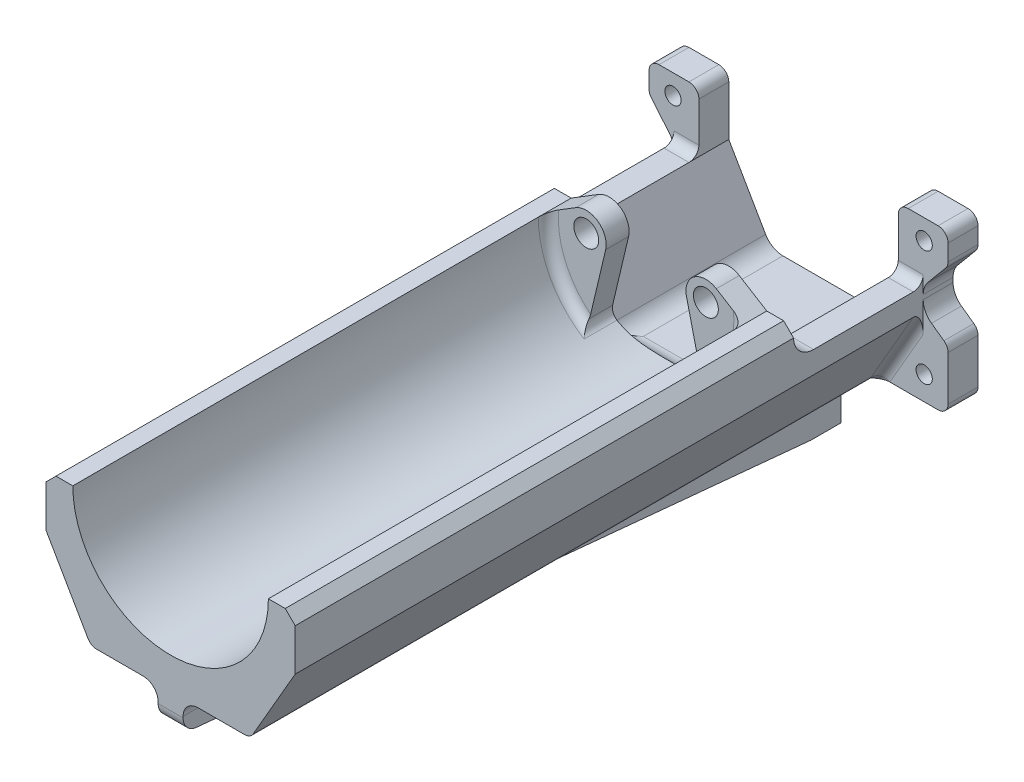
SolidWorks part; units mm, degrees
ref_plane "Front Plane" through (0, 0, 0) normal (0, 0, 1) x (1, 0, 0)
ref_plane "Top Plane" through (0, 0, 0) normal (0, 1, 0) x (1, 0, 0)
ref_plane "Right Plane" through (0, 0, 0) normal (1, 0, 0) x (0, 0, -1)
sketch "Sketch1" plane through (0, 0, 0) normal (0, 0, 1) x (1, 0, 0)
  line L0 (-12.4587, 0) -> (-15.875, 0)
  line L1 (-15.875, 0) -> (-15.875, -16.51)
  line L2 (-15.875, -16.51) -> (15.875, -16.51)
  line L3 (15.875, -16.51) -> (15.875, 0)
  line L4 (15.875, 0) -> (12.4587, 0)
  arc A0 (-12.4587, 0) -> (12.4587, 0) centre (0, 0) ccw
  dimension "D1" = 24.9174
  dimension "D2" = 31.75
  dimension "D3" = 16.51
extrude "Boss-Extrude1" add sketch "Sketch1" along normal blind 63.5
sketch "Sketch2" plane through (0, 0, 0) normal (0, 0, -1) x (-1, 0, 0)
  line L0 (0, 0) -> (0, 50000) construction
  line L1 (-8.9533, 2.1619) -> (-12.4587, 0)
  line L2 (-7.62, 0) -> (0, 0) construction
  line L3 (5.1485, -0.5859) -> (7.3878, -10.032)
  line L5 (-12.4587, 0) -> (-15.875, 0)
  line L6 (-15.875, 0) -> (-15.875, -16.51)
  line L7 (-15.875, -16.51) -> (15.875, -16.51)
  line L8 (15.875, -16.51) -> (15.875, 0)
  line L9 (15.875, 0) -> (12.4587, 0)
  line L10 (-12.4587, 0) -> (-15.875, 0)
  line L11 (-15.875, 0) -> (-15.875, -16.51)
  line L12 (-15.875, -16.51) -> (15.875, -16.51)
  line L13 (15.875, -16.51) -> (15.875, 0)
  line L14 (15.875, 0) -> (12.4587, 0)
  line L16 (-5.1485, -0.5859) -> (-7.3878, -10.032)
  line L17 (8.9533, 2.1619) -> (12.4587, 0)
  circle A0 centre (-7.62, 0) radius 1.5875
  arc A1 (-12.4587, 0) -> (12.4587, 0) centre (0, 0) ccw
  arc A4 (-5.1485, -0.5859) -> (-8.9533, 2.1619) centre (-7.62, 0) ccw
  arc A6 (-12.4587, 0) -> (12.4587, 0) centre (0, 0) ccw construction
  arc A7 (-7.3878, -10.032) -> (7.3878, -10.032) centre (0, 0) ccw
  arc A8 (5.1485, -0.5859) -> (8.9533, 2.1619) centre (7.62, 0) cw
  circle A9 centre (7.62, 0) radius 1.5875
  point P13 (0, 0)
  point P15 (-7.2589, -10.1256)
  dimension "D2" = 3.175
  dimension "D3" = 7.62
  dimension "D4" = 5.08
  dimension "D5" = 45
  dimension "D1" = 0
extrude "Boss-Extrude2" add sketch "Sketch2" against normal blind 2.921
fillet "Fillet1" radius 1.27 4 edges at (11.1189, -5.6204, 2.921) (7.3878, -10.032, 1.4605) (-7.3878, -10.032, 1.4605) (-11.1189, -5.6204, 2.921)
chamfer "Chamfer1" distance 1.27 angle 45 2 edges at (15.875, 0, 31.75) (-15.875, 0, 31.75)
chamfer "Chamfer2" distance 5.715 angle 60 2 edges at (15.875, -16.51, 31.75) (-15.875, -16.51, 31.75)
sketch "Sketch3" plane through (0, 0, 0) normal (0, 0, -1) x (-1, 0, 0)
  line L1 (-15.875, -6.6113) -> (-15.875, -1.27) construction
  line L2 (-7.2741, -13.208) -> (7.2741, -13.208)
  line L4 (15.875, -1.27) -> (15.875, -6.6113) construction
  line L5 (-15.875, -3.81) -> (-15.875, -6.6113)
  line L6 (15.875, -3.81) -> (15.875, -6.6113)
  line L7 (-7.2741, -13.208) -> (-12.7, -3.81)
  line L8 (-12.7, -3.81) -> (-15.875, -3.81)
  line L9 (7.2741, -13.208) -> (12.7, -3.81)
  line L10 (12.7, -3.81) -> (15.875, -3.81)
  line L13 (-15.875, -1.27) -> (-15.875, -6.6113)
  line L14 (-15.875, -6.6113) -> (-10.16, -16.51)
  line L15 (-10.16, -16.51) -> (10.16, -16.51)
  line L16 (10.16, -16.51) -> (15.875, -6.6113)
  line L17 (15.875, -6.6113) -> (15.875, -1.27)
  line L18 (15.875, -1.27) -> (14.605, 0)
  line L19 (14.605, 0) -> (12.4587, 0)
  line L20 (12.4587, 0) -> (8.9533, 2.1619)
  line L21 (5.1485, -0.5859) -> (7.1863, -9.1822)
  line L22 (-7.1863, -9.1822) -> (-5.1485, -0.5859)
  line L23 (-8.9533, 2.1619) -> (-12.4587, 0)
  line L24 (-12.4587, 0) -> (-14.605, 0)
  line L25 (-14.605, 0) -> (-15.875, -1.27)
  line L27 (-15.875, -6.6113) -> (-10.16, -16.51)
  line L28 (-10.16, -16.51) -> (10.16, -16.51)
  line L29 (10.16, -16.51) -> (15.875, -6.6113)
  arc A5 (8.9533, 2.1619) -> (5.1485, -0.5859) centre (7.62, 0) ccw
  arc A6 (6.626, -10.5506) -> (7.1863, -9.1822) centre (5.9506, -9.4751) ccw
  arc A7 (-6.626, -10.5506) -> (6.626, -10.5506) centre (0, 0) ccw
  arc A8 (-7.1863, -9.1822) -> (-6.626, -10.5506) centre (-5.9506, -9.4751) ccw
  arc A9 (-5.1485, -0.5859) -> (-8.9533, 2.1619) centre (-7.62, 0) ccw
  point P16 (13.5589, -3.6592)
  point P30 (10.3427, -13.208)
  point P32 (0, 0)
  point P33 (-14.4971, -3.2928)
  dimension "D2" = 3.302
  dimension "D3" = 3.175
  dimension "D4" = 3.175
  dimension "D5" = 12.7
  dimension "D6" = 12.7
  dimension "D1" = 0
extrude "Boss-Extrude3" add sketch "Sketch3" along normal blind 16.51
sketch "Sketch4" plane through (0, 0, -16.51) normal (0, 0, -1) x (-1, 0, 0)
  line L0 (0, 0) -> (0, 50000) construction
  line L1 (0, 0) -> (50000, 0) construction
  line L7 (0, 0) -> (0, 50000) construction
  line L8 (19.05, -16.51) -> (-19.05, -16.51)
  line L9 (-10.16, -16.51) -> (10.16, -16.51) construction
  line L10 (-19.05, -16.51) -> (-19.05, -8.89)
  line L11 (-19.05, -8.89) -> (-15.875, -6.6113)
  line L13 (-12.7, -3.81) -> (-12.7, 3.81)
  line L14 (-12.7, 3.81) -> (-19.05, 3.81)
  line L15 (-19.05, 3.81) -> (-19.05, 0)
  line L16 (-19.05, 0) -> (-15.875, -3.81)
  line L17 (-15.875, -3.81) -> (-15.875, -6.6113) construction
  line L18 (-12.7, -3.81) -> (-15.875, -3.81) construction
  line L19 (-15.875, -3.81) -> (-15.875, -6.6113)
  line L20 (-12.7, -3.81) -> (-7.2741, -13.208)
  line L21 (-7.2741, -13.208) -> (7.2741, -13.208)
  line L22 (7.2741, -13.208) -> (-7.2741, -13.208) construction
  line L23 (12.7, -3.81) -> (7.2741, -13.208)
  line L24 (15.875, -3.81) -> (15.875, -6.6113)
  line L25 (19.05, 0) -> (15.875, -3.81)
  line L26 (19.05, 3.81) -> (19.05, 0)
  line L27 (12.7, 3.81) -> (19.05, 3.81)
  line L28 (12.7, -3.81) -> (12.7, 3.81)
  line L29 (19.05, -8.89) -> (15.875, -6.6113)
  line L30 (19.05, -16.51) -> (19.05, -8.89)
  arc A0 (-6.626, -10.5506) -> (6.626, -10.5506) centre (0, 0) ccw construction
  point P33 (0, -13.208)
  point P41 (0, -16.51)
  dimension "D1" = 38.1
  dimension "D2" = 38.1
  dimension "D3" = 20.32
  dimension "D4" = 16.51
  dimension "D5" = 7.62
extrude "Boss-Extrude4" add sketch "Sketch4" along normal blind 3.81
sketch "Sketch5" plane through (0, 0, -20.32) normal (0, 0, -1) x (-1, 0, 0)
  line L0 (0, 0) -> (0, 50000) construction
  line L1 (-12.7, 3.81) -> (-19.05, 3.81) construction
  line L2 (-19.05, 3.81) -> (-19.05, 0) construction
  line L3 (-19.05, -8.89) -> (-19.05, -16.51) construction
  line L4 (-19.05, -16.51) -> (19.05, -16.51) construction
  circle A0 centre (-16.002, 1.27) radius 1.035
  circle A1 centre (-16.002, -13.462) radius 1.035
  circle A2 centre (16.002, -13.462) radius 1.035
  circle A3 centre (16.002, 1.27) radius 1.035
  dimension "D3" = 2.0701
  dimension "D4" = 2.0701
  dimension "D1" = 2.54
  dimension "D2" = 3.048
  dimension "D5" = 3.048
  dimension "D6" = 3.048
extrude "Cut-Extrude1" cut sketch "Sketch5" against normal through all
fillet "Fillet2" radius 2.54 5 edges at (-14.2875, -3.81, 0) (14.2875, -3.81, 0) (-7.2741, -13.208, -10.16) (7.2741, -13.208, -10.16) (0, -13.208, 0)
fillet "Fillet3" radius 2.54 4 edges at (-15.875, -6.6113, -18.415) (-15.875, -3.81, -18.415) (15.875, -6.6113, -18.415) (15.875, -3.81, -18.415)
fillet "Fillet4" radius 1.27 12 edges at (10.16, -16.51, 23.495) (-10.16, -16.51, 23.495) (-19.05, -16.51, -18.415) (19.05, -16.51, -18.415) (-19.05, -8.89, -18.415) (19.05, -8.89, -18.415) (-12.7, 3.81, -18.415) (12.7, 3.81, -18.415) (-19.05, 0, -18.415) (-19.05, 3.81, -18.415) (19.05, 0, -18.415) (19.05, 3.81, -18.415)
fillet "Fillet5" radius 1.27 6 edges at (-10.0618, -16.3399, -16.51) (10.0618, -16.3399, -16.51) (-13.2008, -11.2432, -16.51) (13.2008, -11.2432, -16.51) (-14.2875, -3.81, -16.51) (14.2875, -3.81, -16.51)
ref_plane "midplane" through (0, 0, 0) normal (-1, 0, 0) x (0, 0, 1)
sketch "Sketch6" plane through (0, 0, 0) normal (-1, 0, 0) x (0, 0, 1)
  line L0 (63.5, -16.51) -> (-15.24, -16.51) construction
  line L1 (63.5, -16.51) -> (-15.24, -16.51)
  line L2 (-16.51, -16.51) -> (-15.24, -16.51) construction
  line L3 (-16.51, -16.51) -> (-20.32, -16.51) construction
  line L4 (-16.51, -16.51) -> (-15.24, -16.51)
  line L5 (-16.51, -16.51) -> (-20.32, -16.51)
  line L6 (63.5, -16.51) -> (63.5, -20.32)
  line L8 (-20.32, -27.94) -> (-20.32, -16.51)
  line L9 (-20.32, -27.94) -> (-16.51, -27.94)
  line L10 (-16.51, -27.94) -> (63.5, -20.32)
  dimension "D1" = 3.81
  dimension "D2" = 11.43
  dimension "D3" = 3.81
extrude "Boss-Extrude5" add sketch "Sketch6" along normal mid plane 3.175
fillet "Fillet6" radius 1.905 4 edges at (0, -20.32, 63.5) (1.5875, -16.51, 21.59) (0, -27.94, -16.51) (-1.5875, -16.51, 21.59)
equation "\"D4@Sketch5\"=\"D3@Sketch5\""
